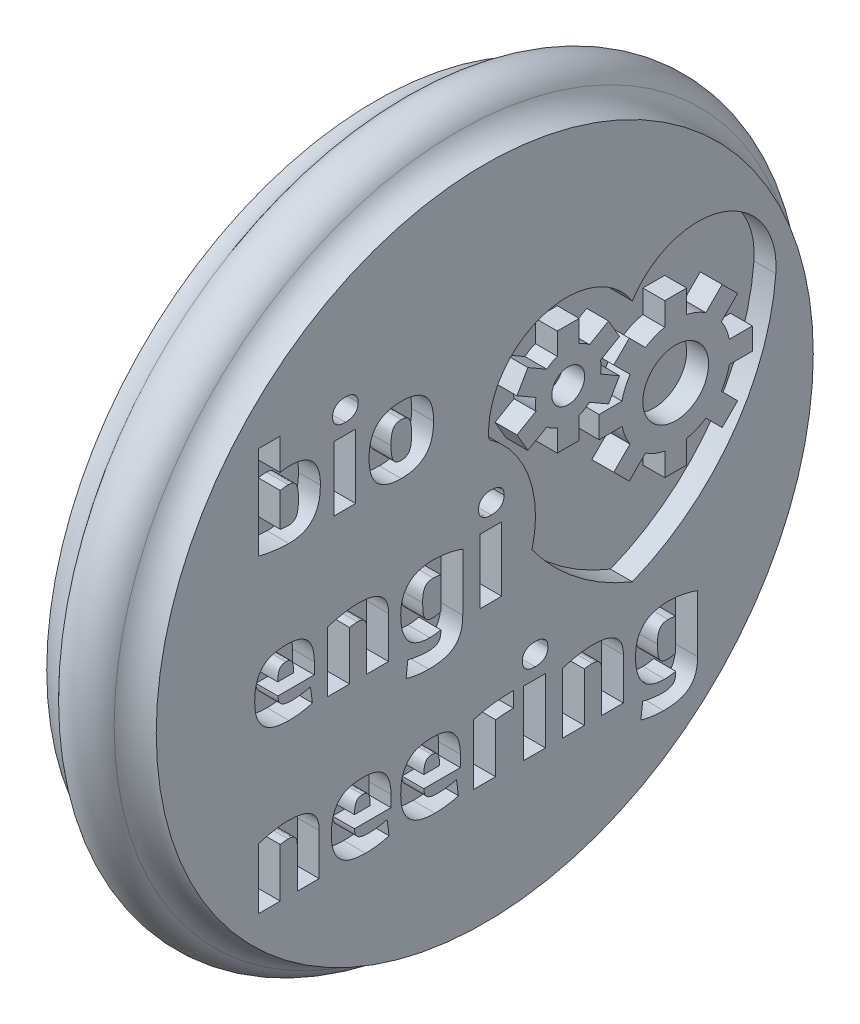
SolidWorks part; units mm, degrees
ref_plane "Alzado" through (0, 0, 0) normal (0, 0, 1) x (1, 0, 0)
ref_plane "Planta" through (0, 0, 0) normal (0, 1, 0) x (1, 0, 0)
ref_plane "Vista lateral" through (0, 0, 0) normal (1, 0, 0) x (0, 0, -1)
sketch "Sketch3" plane through (0, 0, 0) normal (0, 0, 1) x (1, 0, 0)
  line L0 (0, 0) -> (0, 16.7873) construction
  line L1 (2.5, 0) -> (2.5, 15)
  line L2 (-2.5, 0) -> (-2.5, 15)
  line L3 (-2.5, 0) -> (2.5, 0)
  arc A0 (1.25, 15.6708) -> (-1.25, 15.6708) centre (0, 14.8417) ccw
  arc A1 (1.25, 15.6708) -> (2.5, 15) centre (2.5, 16.5) ccw
  arc A2 (-1.25, 15.6708) -> (-2.5, 15) centre (-2.5, 16.5) cw
  dimension "D1" = 3
  dimension "D4" = 3
  dimension "D2" = 15
  dimension "D3" = 2.5
revolve "Revolve1" add sketch "Sketch3" angle 360 about L3
sketch "Sketch4" plane through (-2.5, 0, 0) normal (-1, 0, 0) x (0, 0, 1)
  line L1 (74.3509, 235.2726) -> (407.6843, 235.2726) construction
  line L2 (-10.6534, 2.7336) -> (-9.5782, 1.7539)
  line L3 (-10.6534, 8.0639) -> (-9.5782, 8.0639)
  line L4 (-10.6534, 8.0639) -> (-10.6534, 2.7336)
  line L5 (-9.5782, 1.7539) -> (-4.7756, 1.7539)
  line L6 (-4.7756, 8.0639) -> (-4.7756, 1.7539)
  line L8 (-9.5782, 8.0639) -> (-9.5782, 2.733)
  line L9 (-9.5782, 2.733) -> (-5.8508, 2.733)
  line L10 (-5.8508, 8.0639) -> (-5.8508, 2.733)
  line L11 (-5.8508, 8.0639) -> (-4.7756, 8.0639)
  line L12 (-2.9239, 2.7109) -> (-1.8736, 1.7539)
  line L13 (-2.9239, 9.5707) -> (-1.825, 9.5707)
  line L14 (-2.9239, 9.5707) -> (-2.9239, 11.0136)
  line L15 (-2.9239, 11.0136) -> (-1.825, 11.0136)
  line L16 (-1.825, 9.5707) -> (-1.825, 11.0136)
  line L17 (-2.9239, 8.0639) -> (-1.825, 8.0639)
  line L18 (-2.9239, 8.0639) -> (-2.9239, 2.7109)
  line L19 (-1.8736, 1.7539) -> (2.7209, 1.7539)
  line L20 (2.7209, 2.733) -> (2.7209, 1.7539)
  line L21 (-1.825, 8.0639) -> (-1.825, 2.733)
  line L22 (-1.825, 2.733) -> (2.7209, 2.733)
  line L25 (5.2465, 8.0639) -> (4.1977, 7.096)
  line L26 (10.0535, 1.7539) -> (5.2465, 1.7539)
  line L27 (10.0535, 1.7539) -> (10.0535, 2.733)
  line L28 (10.0535, 8.0639) -> (5.2465, 8.0639)
  line L29 (4.1977, 2.733) -> (4.1977, 7.096)
  line L30 (10.0535, 2.733) -> (5.2465, 2.733)
  line L32 (10.0535, 7.096) -> (5.2465, 7.096)
  line L33 (5.2465, 2.733) -> (5.2465, 7.096)
  line L34 (5.2465, 1.7539) -> (4.1977, 2.733)
  line L35 (10.0535, 7.096) -> (10.0535, 8.0639)
  line L36 (-2.0904, -2.8633) -> (-3.1392, -3.8312)
  line L37 (2.7165, -9.1733) -> (-2.0904, -9.1733)
  line L38 (2.7165, -9.1733) -> (2.7165, -8.1942)
  line L39 (2.7165, -2.8633) -> (-2.0904, -2.8633)
  line L40 (-3.1392, -8.1942) -> (-3.1392, -3.8312)
  line L41 (2.7165, -8.1942) -> (-2.0904, -8.1942)
  line L42 (2.7165, -3.8312) -> (-2.0904, -3.8312)
  line L43 (-2.0904, -8.1942) -> (-2.0904, -3.8312)
  line L44 (-2.0904, -9.1733) -> (-3.1392, -8.1942)
  line L45 (2.7165, -3.8312) -> (2.7165, -2.8633)
  line L46 (-10.6534, 0.0588) -> (-10.6534, -8.1942)
  line L47 (-10.6534, 0.0588) -> (-9.5782, 0.0588)
  line L48 (-9.5782, 0.0588) -> (-9.5782, -2.8633)
  line L49 (-9.5782, -2.8633) -> (-5.8508, -2.8633)
  line L50 (-5.8508, -2.8633) -> (-4.7756, -3.867)
  line L51 (-4.7756, -3.867) -> (-4.7756, -8.1942)
  line L52 (-4.7756, -8.1942) -> (-5.8508, -9.1865)
  line L53 (-5.8508, -9.1865) -> (-9.5782, -9.1865)
  line L54 (-9.5782, -9.1865) -> (-10.6534, -8.1942)
  line L55 (4.1977, -9.1733) -> (4.1977, -2.86)
  line L56 (-9.5782, -3.867) -> (-5.8508, -3.867)
  line L57 (-9.5782, -3.867) -> (-9.5782, -8.1942)
  line L58 (-9.5782, -8.1942) -> (-5.8508, -8.1942)
  line L59 (-5.8508, -3.867) -> (-5.8508, -8.1942)
  line L60 (4.1977, -2.86) -> (8.9432, -2.86)
  line L61 (8.9432, -2.86) -> (10.0535, -3.8887)
  line L62 (10.0535, -3.8887) -> (10.0535, -9.1733)
  line L63 (10.0535, -9.1733) -> (8.9432, -9.1733)
  line L64 (8.9432, -9.1733) -> (8.9432, -3.8347)
  line L65 (8.9432, -3.8347) -> (5.2465, -3.8347)
  line L66 (5.2465, -3.8347) -> (5.2465, -9.1733)
  line L67 (5.2465, -9.1733) -> (4.1977, -9.1733)
extrude "Cut-Extrude1" cut sketch "Sketch4" against normal blind 1
sketch "Sketch5" plane through (2.5, 0, 0) normal (1, 0, 0) x (0, 0, -1)
  line L0 (-10.7265, 4.5333) -> (11.5591, 4.5333) construction
  text T0 "<b>bio</b>\r\n<b>engi</b>\r\n<b>neering</b>" font "3ds" height 4
extrude "Cut-Extrude2" cut sketch "Sketch5" against normal blind 1
sketch "Sketch10" plane through (2.5, 0, 0) normal (1, 0, 0) x (0, 0, -1)
  line L0 (35.0041, 138.7381) -> (263.6708, 138.7381) construction
  line L1 (24.5522, 94.7869) -> (146.5522, 94.7869) construction
  line L2 (123.4623, 351.1969) -> (623.4623, 351.1969) construction
  line L3 (6.7376, -4.9095) -> (6.7376, 6.247) construction
  arc A0 (6.7376, 6.2262) -> (0.1842, 4.0273) centre (3.737, 4.3036) ccw
  arc A1 (0.1842, 4.0273) -> (6.7376, -4.8776) centre (10.6129, 4.8383) ccw
  arc A2 (13.291, 4.0273) -> (6.7376, -4.8776) centre (2.8623, 4.8383) cw
  arc A3 (6.7376, 6.2262) -> (13.291, 4.0273) centre (9.7381, 4.3036) cw
  arc A4 (2.1576, -1.32) -> (0.1842, 4.0273) centre (-2.6833, -0.0687) ccw
  dimension "D1" = 5
extrude "Cut-Extrude3" cut sketch "Sketch10" against normal blind 1 contours A4 A1 A2 A3 A0 region at (2.5, 2.3128, -6.9616)
sketch "Sketch12" plane through (1.5, 0, 0) normal (1, 0, 0) x (0, 0, -1)
  line L0 (8.7191, 1.9972) -> (8.7191, 5.8881) construction
  line L2 (8.2191, 4.4467) -> (8.2191, 5.4972)
  line L3 (8.2191, 5.4972) -> (9.2191, 5.4972)
  line L4 (9.2191, 4.4467) -> (9.2191, 5.4972)
  line L5 (10.0976, 4.0828) -> (10.8404, 4.8256)
  line L6 (10.8404, 4.8256) -> (11.5476, 4.1185)
  line L7 (10.8047, 3.3757) -> (11.5476, 4.1185)
  line L8 (11.1686, 2.4972) -> (12.2191, 2.4972)
  line L9 (12.2191, 2.4972) -> (12.2191, 1.4972)
  line L10 (11.1686, 1.4972) -> (12.2191, 1.4972)
  line L11 (10.8047, 0.6187) -> (11.5476, -0.1241)
  line L12 (11.5476, -0.1241) -> (10.8404, -0.8312)
  line L13 (10.0976, -0.0884) -> (10.8404, -0.8312)
  line L14 (9.2191, -0.4523) -> (9.2191, -1.5028)
  line L15 (9.2191, -1.5028) -> (8.2191, -1.5028)
  line L16 (8.2191, -0.4523) -> (8.2191, -1.5028)
  line L17 (7.3406, -0.0884) -> (6.5978, -0.8312)
  line L18 (6.5978, -0.8312) -> (5.8907, -0.1241)
  line L19 (6.6335, 0.6187) -> (5.8907, -0.1241)
  line L20 (6.2696, 1.4972) -> (5.2191, 1.4972)
  line L21 (5.2191, 1.4972) -> (5.2191, 2.4972)
  line L22 (6.2696, 2.4972) -> (5.2191, 2.4972)
  line L23 (6.6335, 3.3757) -> (5.8907, 4.1185)
  line L24 (5.8907, 4.1185) -> (6.5978, 4.8256)
  line L25 (7.3406, 4.0828) -> (6.5978, 4.8256)
  line L26 (3.8108, 4.3364) -> (3.8108, 6.8595) construction
  line L28 (3.3108, 5.7506) -> (3.3108, 6.7506)
  line L29 (3.3108, 6.7506) -> (4.3108, 6.7506)
  line L30 (4.3108, 5.7506) -> (4.3108, 6.7506)
  line L31 (4.7856, 5.4765) -> (5.6516, 5.9765)
  line L32 (5.6516, 5.9765) -> (6.1516, 5.1105)
  line L33 (5.2856, 4.6105) -> (6.1516, 5.1105)
  line L34 (5.2856, 4.0623) -> (6.1516, 3.5623)
  line L35 (6.1516, 3.5623) -> (5.6516, 2.6962)
  line L36 (4.7856, 3.1962) -> (5.6516, 2.6962)
  line L37 (4.3108, 2.9222) -> (4.3108, 1.9222)
  line L38 (4.3108, 1.9222) -> (3.3108, 1.9222)
  line L39 (3.3108, 2.9222) -> (3.3108, 1.9222)
  line L40 (2.8361, 3.1962) -> (1.97, 2.6962)
  line L41 (1.97, 2.6962) -> (1.47, 3.5623)
  line L42 (2.3361, 4.0623) -> (1.47, 3.5623)
  line L43 (2.3361, 4.6105) -> (1.47, 5.1105)
  line L44 (1.47, 5.1105) -> (1.97, 5.9765)
  line L45 (2.8361, 5.4765) -> (1.97, 5.9765)
  circle A0 centre (8.7191, 1.9972) radius 1.5
  arc A1 (6.6335, 3.3757) -> (6.2696, 2.4972) centre (8.7191, 1.9972) ccw
  arc A2 (8.2191, 4.4467) -> (7.3406, 4.0828) centre (8.7191, 1.9972) ccw
  arc A3 (10.0976, 4.0828) -> (9.2191, 4.4467) centre (8.7191, 1.9972) ccw
  arc A4 (11.1686, 2.4972) -> (10.8047, 3.3757) centre (8.7191, 1.9972) ccw
  arc A5 (10.8047, 0.6187) -> (11.1686, 1.4972) centre (8.7191, 1.9972) ccw
  arc A6 (9.2191, -0.4523) -> (10.0976, -0.0884) centre (8.7191, 1.9972) ccw
  arc A7 (7.3406, -0.0884) -> (8.2191, -0.4523) centre (8.7191, 1.9972) ccw
  arc A8 (6.2696, 1.4972) -> (6.6335, 0.6187) centre (8.7191, 1.9972) ccw
  circle A9 centre (3.8108, 4.3364) radius 0.75
  arc A10 (3.3108, 5.7506) -> (2.8361, 5.4765) centre (3.8108, 4.3364) ccw
  arc A11 (4.7856, 5.4765) -> (4.3108, 5.7506) centre (3.8108, 4.3364) ccw
  arc A12 (5.2856, 4.0623) -> (5.2856, 4.6105) centre (3.8108, 4.3364) ccw
  arc A13 (4.3108, 2.9222) -> (4.7856, 3.1962) centre (3.8108, 4.3364) ccw
  arc A14 (2.8361, 3.1962) -> (3.3108, 2.9222) centre (3.8108, 4.3364) ccw
  arc A15 (2.3361, 4.6105) -> (2.3361, 4.0623) centre (3.8108, 4.3364) ccw
  point P38 (8.7191, 1.9972)
  point P63 (3.8108, 4.3364)
  dimension "D1" = 3
  dimension "D2" = 5
  dimension "D7" = 1.5
  dimension "D8" = 3
  dimension "D3" = 3.5
  dimension "D4" = 1
  dimension "D5" = 0.5
  dimension "D9" = 1
  dimension "D10" = 1
  dimension "D11" = 1
  dimension "D6" = 8
  dimension "D12" = 6
extrude "Boss-Extrude6" add sketch "Sketch12" along normal blind 1 contours L43 A15 L42 L41 L40 A14 L39 L38 L37 A13 L36 L35 L34 A12 L33 L32 L31 A11 L30 L29 L28 A10 L45 L44 A9 | L20 A8 L19 L18 L17 A7 L16 L15 L14 A6 L13 L12 L11 A5 L10 L9 L8 A4 L7 L6 L5 A3 L4 L3 L2 A2 L25 L24 L23 A1 L22 L21 A0 region at (1.5, 4.972, -8.3181) region at (1.5, 6.2506, -3.3781)
